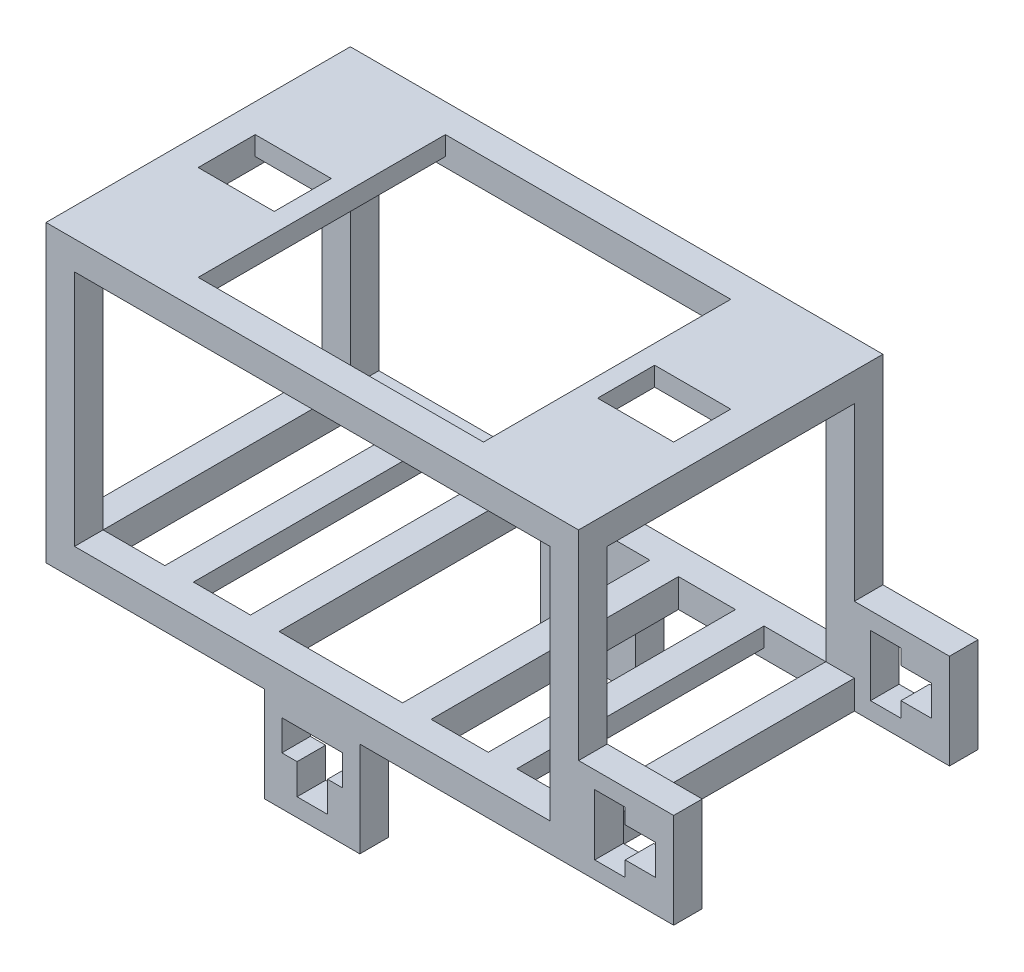
SolidWorks part; units mm, degrees
ref_plane "Front" through (0, 0, 0) normal (0, 0, 1) x (1, 0, 0)
ref_plane "Top" through (0, 0, 0) normal (0, 1, 0) x (1, 0, 0)
ref_plane "Right" through (0, 0, 0) normal (1, 0, 0) x (0, 0, -1)
sketch "Sketch1" plane through (0, 0, 0) normal (0, 1, 0) x (1, 0, 0)
  line L0 (28, 16) -> (-28, 16)
  line L1 (25, -13) -> (-25, -13)
  line L2 (25, -13) -> (25, 13)
  line L3 (25, 13) -> (-25, 13)
  line L4 (-25, -13) -> (-25, 13)
  line L5 (0, 13) -> (0, -13) construction
  line L6 (25, 0) -> (-25, 0) construction
  line L7 (-28, -16) -> (-28, 16)
  line L8 (28, -16) -> (-28, -16)
  line L9 (28, -16) -> (28, 16)
  point P0 (0, 0)
  dimension "D1" = 50
  dimension "D2" = 26
  dimension "D3" = 3
extrude "Boss-Extrude1" add sketch "Sketch1" along normal blind 3
sketch "Sketch2" plane through (0, 0, 0) normal (0, 1, 0) x (1, 0, 0)
  line L0 (-50, 0) -> (50, 0) construction
  line L1 (28, 16) -> (25, 16)
  line L2 (28, 16) -> (28, 13)
  line L3 (28, 13) -> (25, 13)
  line L4 (25, 16) -> (25, 13)
  line L5 (28, -13) -> (25, -13)
  line L6 (25, -16) -> (25, -13)
  line L7 (28, -16) -> (25, -16)
  line L8 (28, -16) -> (28, -13)
  line L9 (0, -50) -> (0, 50) construction
  line L10 (-28, -16) -> (-25, -16)
  line L11 (-25, -16) -> (-25, -13)
  line L12 (-28, -16) -> (-28, -13)
  line L13 (-28, -13) -> (-25, -13)
  line L14 (-25, 16) -> (-25, 13)
  line L15 (-28, 13) -> (-25, 13)
  line L16 (-28, 16) -> (-28, 13)
  line L17 (-28, 16) -> (-25, 16)
extrude "Boss-Extrude2" add sketch "Sketch2" along normal blind 28
sketch "Sketch3" plane through (0, 0, 16) normal (0, 0, 1) x (1, 0, 0)
  line L0 (50, 0) -> (-50, 0) construction
  line L1 (28, 0) -> (38, 0)
  line L2 (28, 0) -> (28, 10)
  line L3 (28, 10) -> (38, 10)
  line L4 (38, 0) -> (38, 10)
  line L5 (28, 28) -> (28, 0) construction
  line L6 (38, 10) -> (38, 5)
  line L7 (38, 5) -> (28, 5)
  line L8 (38, 5) -> (36.1, 5)
  line L9 (36.1, 3.4) -> (36.1, 6.6)
  line L10 (32.9, 3.4) -> (32.9, 1.8)
  line L11 (36.1, 6.6) -> (32.9, 6.6)
  line L12 (36.1, 6.6) -> (36.1, 3.4)
  line L13 (36.1, 3.4) -> (32.9, 3.4)
  line L14 (32.9, 6.6) -> (32.9, 3.4)
  line L16 (32.9, 1.8) -> (29.7, 1.8)
  line L17 (32.9, 1.8) -> (32.9, 8.2)
  line L18 (32.9, 8.2) -> (29.7, 8.2)
  line L19 (29.7, 1.8) -> (29.7, 8.2)
  line M10 (28, 0) -> (28, 28)
  dimension "D1" = 10
  dimension "D2" = 10
  dimension "D3" = 1.9
  dimension "D4" = 1.6
  dimension "D5" = 3.2
  dimension "D6" = 1.6
  dimension "D7" = 3.2
  dimension "D8" = 6.4
  dimension "D9" = 1.6
extrude "Boss-Extrude3" add sketch "Sketch3" against normal blind 3 contours L7 L19 L18 L17 L11 L9 L4 L3 L2 | L16 L19 L7 L1 L4 L9 L13 L10 M10 region at (33.2808, 1.9827, 16) region at (33.2808, 8.0173, 16)
mirror "Mirror1" about plane through (0, 0, 0) normal (0, 0, 1) of "Boss-Extrude3"
sketch "Sketch4" plane through (0, 0, 16) normal (0, 0, 1) x (1, 0, 0)
  line L0 (0, 0) -> (5, 0)
  line L1 (50, 0) -> (-50, 0) construction
  line L2 (0, -10) -> (0, -8.1)
  line L3 (5, 0) -> (-5, 0)
  line L4 (5, 0) -> (5, -10)
  line L5 (5, -10) -> (-5, -10)
  line L6 (-5, 0) -> (-5, -10)
  line L9 (0, -8.1) -> (1.6, -8.1)
  line L10 (1.6, -8.1) -> (-1.6, -8.1)
  line L11 (1.6, -4.9) -> (3.2, -4.9)
  line L12 (-1.6, -8.1) -> (1.6, -8.1)
  line L13 (-1.6, -8.1) -> (-1.6, -4.9)
  line L14 (-1.6, -4.9) -> (1.6, -4.9)
  line L15 (1.6, -8.1) -> (1.6, -4.9)
  line L17 (3.2, -4.9) -> (-3.2, -4.9)
  line L18 (3.2, -4.9) -> (3.2, -1.7)
  line L19 (3.2, -1.7) -> (-3.2, -1.7)
  line L20 (-3.2, -4.9) -> (-3.2, -1.7)
  line M10 (-28, 0) -> (38, 0)
  dimension "D1" = 5
  dimension "D2" = 10
  dimension "D3" = 10
  dimension "D4" = 1.9
  dimension "D5" = 1.6
  dimension "D6" = 3.2
  dimension "D7" = 3.2
  dimension "D8" = 1.6
  dimension "D9" = 3.2
  dimension "D10" = 1.6
extrude "Boss-Extrude4" add sketch "Sketch4" against normal blind 3 contours L17 L20 L19 L18 L11 L15 L9 L5 L4 L6 L10 L13 M10 region at (2.5, -0.1414, 16)
mirror "Mirror2" about plane through (0, 0, 0) normal (0, 0, 1) of "Boss-Extrude4"
sketch "Sketch6" plane through (0, 28, 0) normal (0, 1, 0) x (1, 0, 0)
  line L0 (-28, 16) -> (-28, 13) construction
  line L1 (28, -16) -> (-28, -16)
  line L2 (28, -16) -> (28, 16)
  line L3 (28, 16) -> (-28, 16)
  line L4 (-28, -16) -> (-28, 16)
  line L5 (-25, 16) -> (-28, 16) construction
  line L6 (-25, -9) -> (-25, 9)
  line L7 (-25, 13) -> (25, 13)
  line L8 (-25, 13) -> (-25, -13)
  line L9 (-25, -13) -> (25, -13)
  line L10 (25, 13) -> (25, -13)
  line L11 (-50, 0) -> (50, 0) construction
  line L13 (-25, 9) -> (-25, 6)
  line L15 (25, 9) -> (25, 6)
  point P23 (-25, 0)
  line M1 (28, -16) -> (28, -13)
  line M2 (28, -13) -> (25, -13)
  line M3 (25, -13) -> (25, -16)
  line M4 (25, -16) -> (28, -16)
  dimension "D1" = 9
  dimension "D2" = 3
extrude "Boss-Extrude5" add sketch "Sketch6" along normal blind 3 contours M4 M1 M2 M3 | L7 L10 L2 L3 L4 L1 L9 L8 L6 M2 M3 region at (26.5, 28, 14.5) region at (-1.5, 28, 15.355)
sketch "Sketch10" plane through (0, 3, 0) normal (0, 1, 0) x (1, 0, 0)
  line L0 (0, 13) -> (-6.5, 13)
  line L1 (-25, 13) -> (25, 13) construction
  line L2 (-25, -13) -> (25, -13) construction
  line L3 (-6.5, 13) -> (-9.5, 13)
  line L4 (-6.5, 13) -> (-6.5, -13)
  line L5 (-6.5, -13) -> (-9.5, -13)
  line L6 (-9.5, 13) -> (-9.5, -13)
  line L7 (-9.5, 13) -> (-15.5, 13)
  line L8 (0, -50) -> (0, 50) construction
  line L9 (-15.5, 13) -> (-18.5, 13)
  line L10 (-15.5, 13) -> (-15.5, -13)
  line L11 (-15.5, -13) -> (-18.5, -13)
  line L12 (-18.5, 13) -> (-18.5, -13)
  line L13 (15.5, -13) -> (18.5, -13)
  line L14 (18.5, 13) -> (18.5, -13)
  line L15 (15.5, 13) -> (18.5, 13)
  line L16 (15.5, 13) -> (15.5, -13)
  line L17 (6.5, -13) -> (9.5, -13)
  line L18 (9.5, 13) -> (9.5, -13)
  line L19 (6.5, 13) -> (9.5, 13)
  line L20 (6.5, 13) -> (6.5, -13)
  dimension "D1" = 6.5
  dimension "D2" = 3
  dimension "D3" = 6
  dimension "D4" = 3
extrude "Boss-Extrude7" add sketch "Sketch10" against normal blind 3 contours L19 L20 L17 L18 | L3 L6 L5 L4 region at (-8, 3, 0) region at (8, 3, 0)
extrude "Boss-Extrude8" add sketch "Sketch10<4>" against normal blind 2 contours L15 L16 L13 L14 | L9 L12 L11 L10 region at (-17, 3, 0) region at (17, 3, 0)
sketch "Sketch10<4>" plane through (0, 3, 0) normal (0, 1, 0) x (1, 0, 0) same geometry as "Sketch10"
sketch "Sketch11" plane through (0, 31, 0) normal (0, 1, 0) x (1, 0, 0)
  line L0 (-25, 13) -> (25, 13) construction
  line L1 (-25, -13) -> (-15, -13)
  line L2 (-25, -13) -> (-25, 13)
  line L3 (-25, 13) -> (-15, 13)
  line L4 (-15, -13) -> (-15, 13)
  line L5 (-25, 0) -> (-25, -3)
  line L6 (-50, 0) -> (50, 0) construction
  line L7 (0, -50) -> (0, 50) construction
  line L8 (-25, -3) -> (-15, -3)
  line L9 (-25, -3) -> (-25, 3)
  line L10 (-25, 3) -> (-15, 3)
  line L11 (-15, -3) -> (-15, 3)
  line L12 (25, 3) -> (15, 3)
  line L13 (15, -3) -> (15, 3)
  line L14 (25, -3) -> (15, -3)
  line L15 (25, -3) -> (25, 3)
  line L16 (25, 13) -> (15, 13)
  line L17 (15, -13) -> (15, 13)
  line L18 (25, -13) -> (15, -13)
  line L19 (25, -13) -> (25, 13)
  line L20 (15, -3) -> (17, -3)
  line L21 (17, -3) -> (17, 3)
  line L22 (-17, -3) -> (-17, 3)
  line M9 (25, 13) -> (25, -13)
  line M10 (25, -13) -> (-25, -13)
  line M11 (-25, -13) -> (-25, 13)
  line M12 (-25, 13) -> (25, 13)
  dimension "D1" = 10
  dimension "D2" = 3
  dimension "D3" = 6
  dimension "D4" = 2
extrude "Boss-Extrude9" add sketch "Sketch11" against normal blind 2 contours L17 L14 M10 M9 | L14 L21 L12 L13 | L17 L12 M9 M12 | L2 L10 L4 M12 | L8 L4 M11 M10 | L22 L8 L4 L10 region at (-20, 31, 8) region at (-16, 31, 0) region at (20, 31, 8) region at (-20, 31, -8) region at (16, 31, 0) region at (20, 31, -8)
